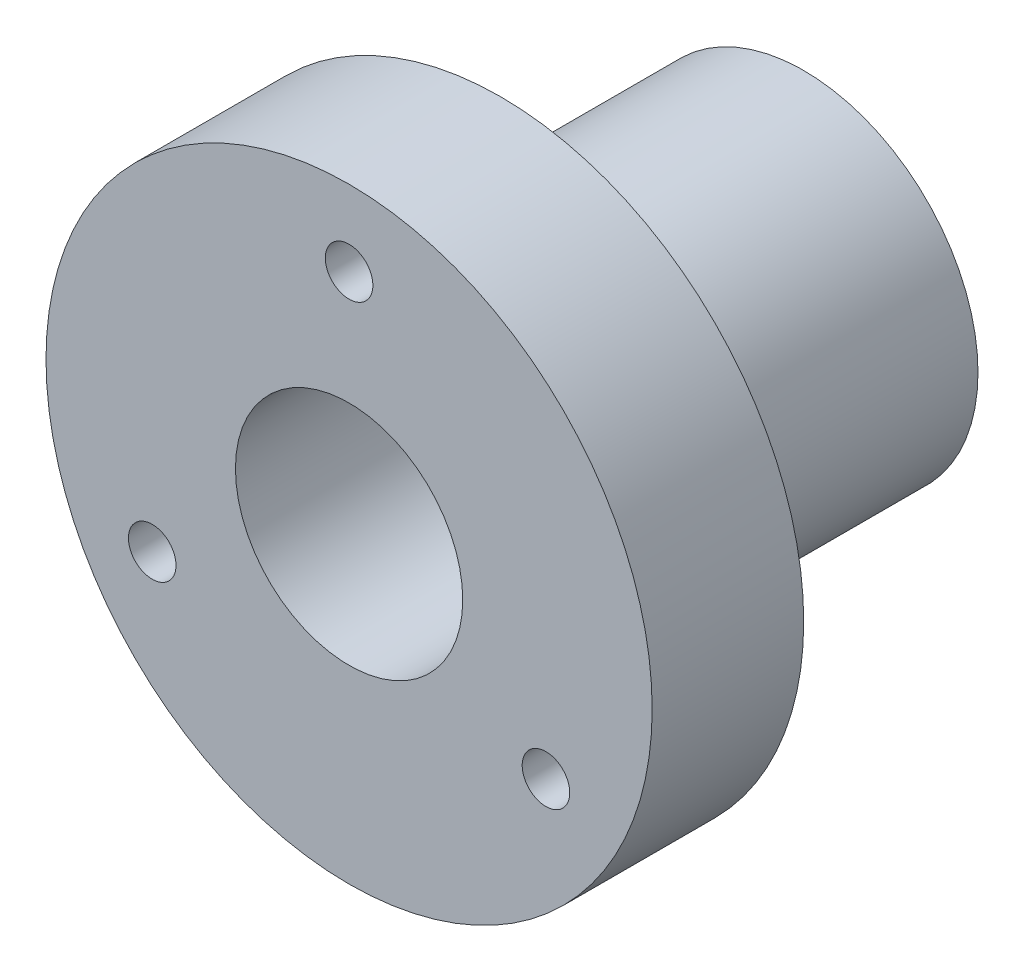
SolidWorks part; units mm, degrees
material "1060 Alloy"
ref_plane "Front" through (0, 0, 0) normal (0, 0, 1) x (1, 0, 0)
ref_plane "Top" through (0, 0, 0) normal (0, 1, 0) x (1, 0, 0)
ref_plane "Right" through (0, 0, 0) normal (1, 0, 0) x (0, 0, -1)
sketch "Sketch1" plane through (0, 0, 0) normal (0, 0, 1) x (1, 0, 0)
  circle A0 centre (0, 0) radius 25.4
  dimension "D1" = 50.8
extrude "Boss-Extrude1" add sketch "Sketch1" against normal blind 12.7
sketch "Sketch9" plane through (0, 0, 0) normal (0, 0, 1) x (1, 0, 0)
  circle A0 centre (0, 0) radius 14.605
  dimension "D1" = 29.21
extrude "Boss-Extrude2" add sketch "Sketch9" against normal blind 38.1
sketch "Sketch10" plane through (0, 0, -12.7) normal (0, 0, -1) x (-1, 0, 0)
  circle A0 centre (0, 0) radius 19.05 construction
  dimension "D1" = 38.1
hole_wizard "#10-24 Tapped Hole1" positions "Sketch11" profile "Sketch12" tap size "#10-24" standard "ANSI Inch" end condition through all
sketch "Sketch11" plane through (0, 0, -12.7) normal (0, 0, -1) x (-1, 0, 0)
  circle A0 centre (0, 0) radius 19.05 construction
  point P0 (0, 19.05)
  point P4 (-16.4978, -9.525)
  point P6 (16.4978, -9.525)
  dimension "D1" = 120
  dimension "D2" = 120
cosmetic thread "Hole Thread4" parameters "D2"=4.826
cosmetic thread "Hole Thread5" parameters "D2"=4.826
cosmetic thread "Hole Thread6" parameters "D2"=4.826
sketch "Sketch12" plane through (0, 19.05, -12.7) normal (1, 0, 0) x (0, 1, 0)
  line L0 (0, 0) -> (0, 12.7)
  line L1 (0, 12.7) -> (1.9939, 12.7)
  line L2 (1.9939, 12.7) -> (1.9939, 0)
  line L5 (1.9939, 0) -> (0, 0)
  line L11 (0, -6.35) -> (0, 107.95) construction
  dimension "Thru Tap Drill Dia." = 3.9878
  dimension "Thru Tap Drill Depth" = 12.7
hole_wizard "Ø8.4 (8.4) Diameter Hole2" positions "Sketch13" profile "Sketch14" hole size "Ø8.4" standard "ANSI Metric" end condition through all
sketch "Sketch13" plane through (0, 0, -38.1) normal (0, 0, -1) x (-1, 0, 0)
  point P0 (0, 0)
sketch "Sketch14" plane through (0, 0, -38.1) normal (1, 0, 0) x (0, 1, 0)
  line L0 (0, 0) -> (0, 38.1)
  line L1 (0, 38.1) -> (4.2, 38.1)
  line L2 (4.2, 38.1) -> (4.2, 0)
  line L5 (4.2, 0) -> (0, 0)
  line L11 (0, -6.35) -> (0, 107.95) construction
  dimension "Thru Hole Dia." = 8.4
  dimension "Thru Hole Depth" = 38.1
hole_wizard "Ø10.0 (10) Diameter Hole1" positions "Sketch15" profile "Sketch16" hole size "Ø10.0" standard "ANSI Metric"
sketch "Sketch15" plane through (0, 0, -38.1) normal (0, 0, -1) x (-1, 0, 0)
  point P0 (0, 0)
sketch "Sketch16" plane through (0, 0, -38.1) normal (1, 0, 0) x (0, 1, 0)
  line L0 (0, 0) -> (0, 13.1643)
  line L1 (0, 13.1643) -> (5, 10.16)
  line L2 (5, 10.16) -> (5, 0)
  line L5 (5, 0) -> (0, 0)
  line L10 (0, 13.1643) -> (-5, 10.16) construction
  line L11 (0, -6.35) -> (0, 107.95) construction
  dimension "Hole Dia." = 10
  dimension "Hole Depth" = 10.16
  dimension "Drill Angle" = 118
hole_wizard "3/4 (0.75) Diameter Hole1" positions "Sketch17" profile "Sketch18" hole size "3/4" standard "ANSI Inch"
sketch "Sketch17" plane through (0, 0, 0) normal (0, 0, 1) x (1, 0, 0)
  point P0 (0, 0)
sketch "Sketch18" plane through (0, 0, 0) normal (1, 0, 0) x (0, -1, 0)
  line L0 (0, 0) -> (0, 22.86)
  line L1 (0, 22.86) -> (9.525, 22.86)
  line L2 (9.525, 22.86) -> (9.525, 0)
  line L5 (9.525, 0) -> (0, 0)
  line L10 (0, 22.86) -> (-9.525, 22.86) construction
  line L11 (0, -6.35) -> (0, 107.95) construction
  dimension "Hole Dia." = 19.05
  dimension "Hole Depth" = 22.86
  dimension "Drill Angle" = 180
